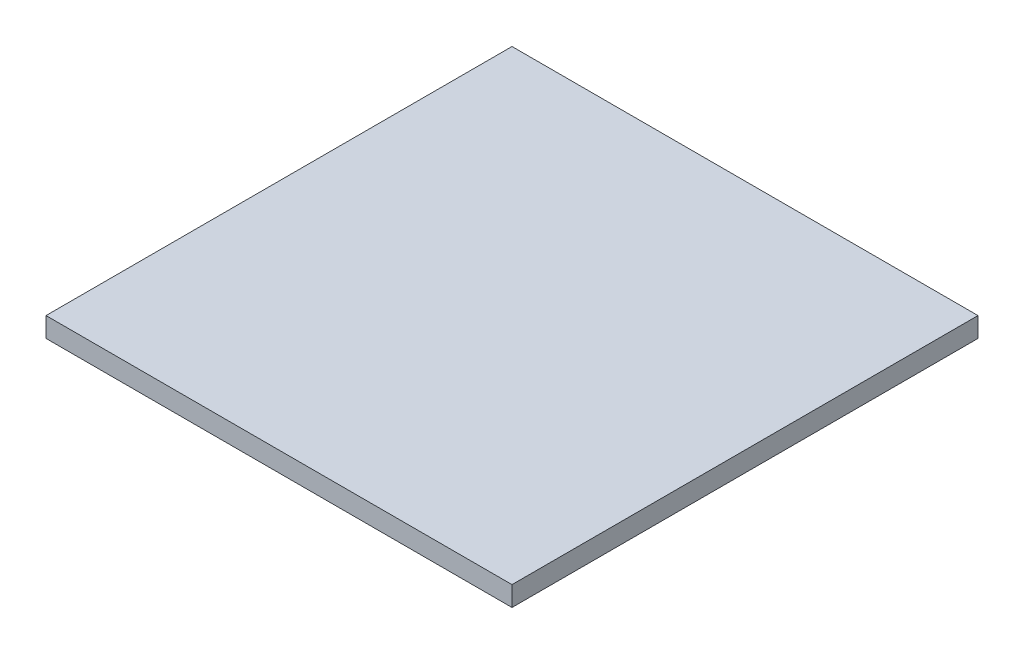
SolidWorks part; units mm, degrees
material "1060 Alloy"
ref_plane "Front Plane" through (0, 0, 0) normal (0, 0, 1) x (1, 0, 0)
ref_plane "Top Plane" through (0, 0, 0) normal (0, 1, 0) x (1, 0, 0)
ref_plane "Right Plane" through (0, 0, 0) normal (1, 0, 0) x (0, 0, -1)
sketch "Sketch1" plane through (0, 0, 0) normal (0, 1, 0) x (1, 0, 0)
  line L1 (-47, -47) -> (47, -47)
  line L2 (-47, -47) -> (-47, 47)
  line L3 (-47, 47) -> (47, 47)
  line L4 (47, -47) -> (47, 47)
  line L5 (-47, -47) -> (47, 47) construction
  line L6 (-47, 47) -> (47, -47) construction
  point P0 (0, 0)
  dimension "D1" = 94
  dimension "D2" = 94
extrude "Boss-Extrude1" add sketch "Sketch1" along normal blind 4
sketch "Sketch2" plane through (0, 4, 0) normal (0, 1, 0) x (1, 0, 0)
  line L1 (-19, -19) -> (19, -19)
  line L2 (-19, -19) -> (-19, 19)
  line L3 (-19, 19) -> (19, 19)
  line L4 (19, -19) -> (19, 19)
  line L5 (-19, -19) -> (19, 19) construction
  line L6 (-19, 19) -> (19, -19) construction
  point P0 (0, 0)
  dimension "D1" = 38
